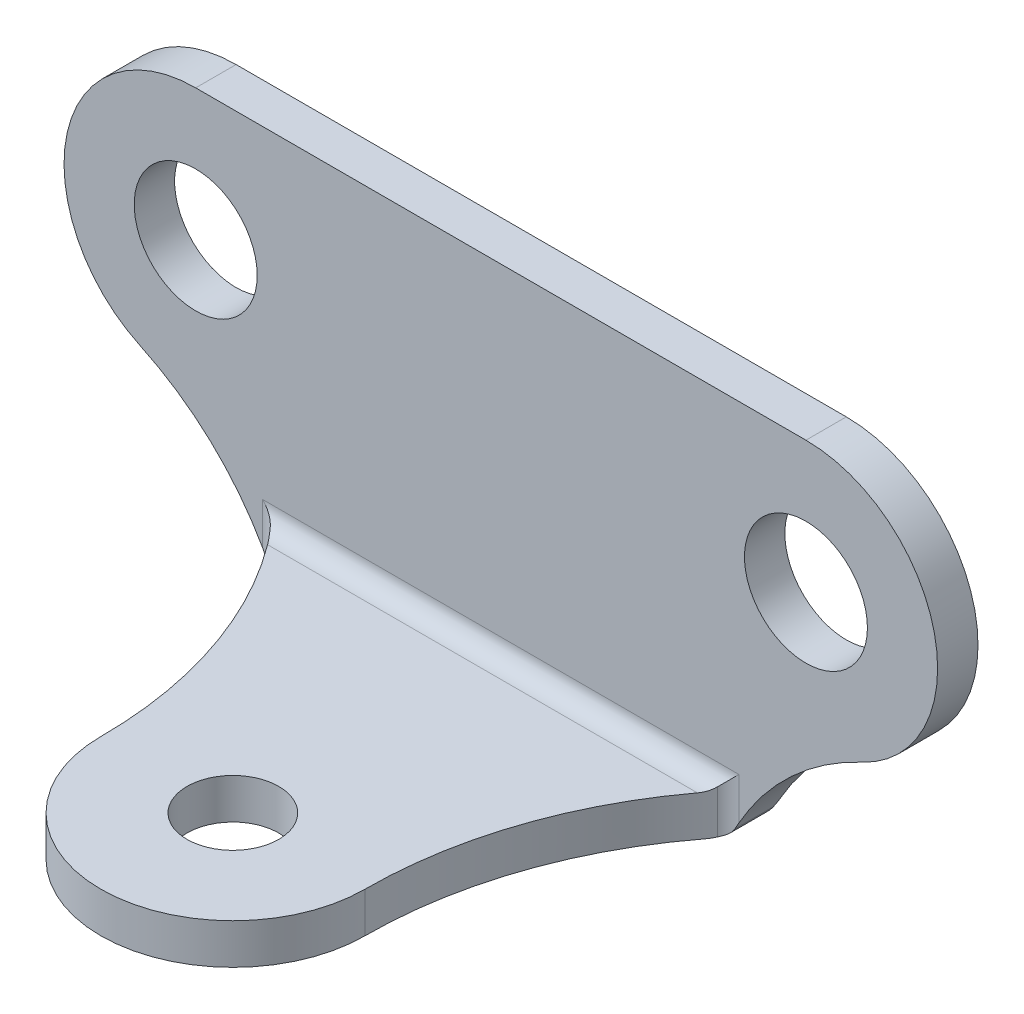
SolidWorks part; units mm, degrees
ref_plane "Plano frontal" through (0, 0, 0) normal (0, 0, 1) x (1, 0, 0)
ref_plane "Plano superior" through (0, 0, 0) normal (0, 1, 0) x (1, 0, 0)
ref_plane "Plano direito" through (0, 0, 0) normal (1, 0, 0) x (0, 0, -1)
sketch "Esboço1" plane through (0, 0, 0) normal (0, 0, 1) x (1, 0, 0)
  line L0 (-16.625, 0) -> (16.625, 0) construction
  line L1 (-16.625, 7.175) -> (16.625, 7.175)
  line L2 (0, 0) -> (0, 7.175) construction
  line L3 (-12.5, -13.625) -> (12.5, -13.625)
  circle A0 centre (-16.625, 0) radius 3.35
  circle A1 centre (16.625, 0) radius 3.35
  arc A2 (-19.6719, -6.4959) -> (-16.625, 7.175) centre (-16.625, 0) cw
  arc A3 (19.6719, -6.4959) -> (16.625, 7.175) centre (16.625, 0) ccw
  arc A4 (-19.6719, -6.4959) -> (-12.5, -13.625) centre (-26.0419, -20.0762) cw
  arc A5 (19.6719, -6.4959) -> (12.5, -13.625) centre (26.0419, -20.0762) ccw
  point P16 (23.8, 0)
  point P20 (-23.8, 0)
  dimension "D2" = 6.7
  dimension "D6" = 15
  dimension "D1" = 33.25
  dimension "D3" = 20.8
  dimension "D4" = 47.6
  dimension "D5" = 25
extrude "Ressalto-extrusão1" add sketch "Esboço1" along normal blind 2.2 contours A5 A3 L1 A2 A4 L3 A1 A0 region at (0, -2.5731, 0)
sketch "Esboço2" plane through (0, 0, 2.2) normal (0, 0, 1) x (1, 0, 0)
  line L1 (-12.5, -13.625) -> (12.5, -13.625)
  line L2 (-12.5, -13.625) -> (-12.5, -11.425)
  line L3 (-12.5, -11.425) -> (12.5, -11.425)
  line L4 (12.5, -13.625) -> (12.5, -11.425)
  line L5 (-12.5, -13.625) -> (12.5, -13.625) construction
  point P5 (12.5, -13.625)
  point P6 (-12.4938, -13.625)
  point P7 (0, 0)
  point P11 (-12.5, -13.625)
  line M10 (-12.5, -13.625) -> (12.5, -13.625)
  dimension "D1" = 2.2
extrude "Ressalto-extrusão2" add sketch "Esboço2" along normal blind 21.8 contours L3 M10 region at (0, -12.525, 2.2)
sketch "Esboço3" plane through (0, -13.625, 0) normal (0, -1, 0) x (1, 0, 0)
  line L0 (-12.5, 0) -> (12.5, 0) construction
  line L2 (0, 16.8) -> (0, 0) construction
  line L3 (-12.5, 24) -> (12.5, 24) construction
  circle A0 centre (0, 16.8) radius 2.5
  arc A1 (-7.2, 16.8) -> (-12.5, 2.2) centre (-29.9594, 16.8) cw
  arc A2 (-7.2, 16.8) -> (7.2, 16.8) centre (0, 16.8) cw
  arc A3 (7.2, 16.8) -> (12.5, 2.2) centre (29.9594, 16.8) ccw
  dimension "D1" = 5
  dimension "D2" = 16.8
extrude "Corte-extrusão2" cut sketch "Esboço3" against normal blind 24 and the other way through all
fillet "Filete1" radius 1 6 edges at (12.5, -13.625, 1.1) (12.5, -12.525, 2.2) (0, -13.625, 0) (0, -11.425, 2.2)
